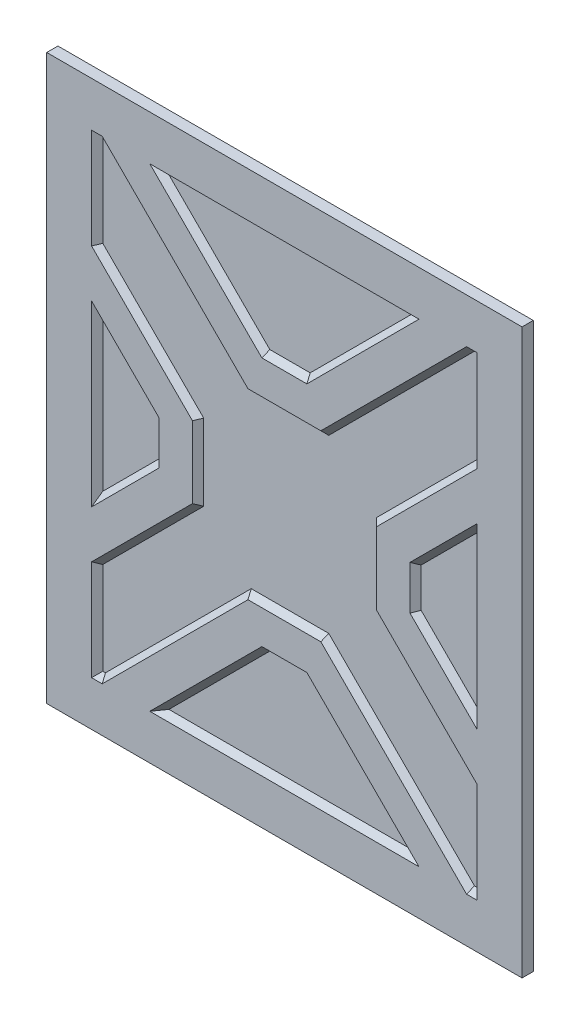
SolidWorks part; units mm, degrees
ref_plane "Plan de face" through (0, 0, 0) normal (0, 0, 1) x (1, 0, 0)
ref_plane "Plan de dessus" through (0, 0, 0) normal (0, 1, 0) x (1, 0, 0)
ref_plane "Plan de droite" through (0, 0, 0) normal (1, 0, 0) x (0, 0, -1)
sketch "Esquisse1" plane through (0, 0, 0) normal (0, 0, 1) x (1, 0, 0)
  line L1 (0, 0) -> (424, 0)
  line L2 (0, 0) -> (0, 503)
  line L3 (0, 503) -> (424, 503)
  line L4 (424, 0) -> (424, 503)
  dimension "D1" = 503
  dimension "D2" = 424
extrude "Boss.-Extru.1" add sketch "Esquisse1" along normal blind 10
sketch "Esquisse2" plane through (0, 0, 10) normal (0, 0, 1) x (1, 0, 0)
  line L0 (179.4975, 333) -> (130, 283.5025) construction
  line L1 (100, 231.9239) -> (100, 271.0761)
  line L2 (100, 271.0761) -> (40, 331.0761)
  line L3 (191.9239, 363) -> (232.0761, 363)
  line L4 (212, 463) -> (212, 40) construction
  line L5 (384, 251.5) -> (40, 251.5) construction
  line L6 (40, 463) -> (40, 373.5025)
  line L7 (40, 373.5025) -> (130, 283.5025)
  line L8 (40, 463) -> (40, 40)
  line L9 (40, 40) -> (384, 40)
  line L10 (384, 40) -> (384, 463)
  line L11 (384, 463) -> (40, 463)
  line L12 (40, 463) -> (40, 40) construction
  line L13 (40, 40) -> (384, 40) construction
  line L14 (384, 40) -> (384, 463) construction
  line L15 (384, 463) -> (40, 463) construction
  line L16 (130, 283.5025) -> (130, 219.4975)
  line L17 (40, 463) -> (49.4975, 463)
  line L18 (49.4975, 463) -> (179.4975, 333)
  line L19 (244.5025, 333) -> (179.4975, 333)
  line L20 (332.0761, 463) -> (91.9239, 463)
  line L21 (91.9239, 463) -> (191.9239, 363)
  line L22 (294, 283.5025) -> (294, 219.4975)
  line L23 (40, 331.0761) -> (40, 171.9239)
  line L24 (324, 231.9239) -> (324, 271.0761)
  line L25 (130, 283.5025) -> (130, 333) construction
  line L26 (130, 333) -> (179.4975, 333) construction
  line L27 (324, 271.0761) -> (384, 331.0761)
  line L28 (384, 331.0761) -> (384, 171.9239)
  line L29 (384, 373.5025) -> (294, 283.5025)
  line L30 (384, 463) -> (384, 373.5025)
  line L31 (384, 463) -> (374.5025, 463)
  line L32 (374.5025, 463) -> (244.5025, 333)
  line L33 (332.0761, 463) -> (232.0761, 363)
  line L34 (100, 231.9239) -> (40, 171.9239)
  line L35 (40, 129.4975) -> (130, 219.4975)
  line L36 (384, 40) -> (374.5025, 40)
  line L37 (384, 40) -> (384, 129.4975)
  line L38 (40, 40) -> (40, 129.4975)
  line L39 (40, 40) -> (49.4975, 40)
  line L40 (332.0761, 40) -> (91.9239, 40)
  line L41 (191.9239, 140) -> (232.0761, 140)
  line L42 (244.5025, 170) -> (179.4975, 170)
  line L43 (91.9239, 40) -> (191.9239, 140)
  line L44 (49.4975, 40) -> (179.4975, 170)
  line L45 (332.0761, 40) -> (232.0761, 140)
  line L46 (374.5025, 40) -> (244.5025, 170)
  line L47 (384, 129.4975) -> (294, 219.4975)
  line L48 (324, 231.9239) -> (384, 171.9239)
  point P20 (212, 333)
  point P23 (294, 251.5)
  point P31 (212, 363)
  point P33 (100, 251.5)
  point P34 (130, 251.5)
  point P47 (324, 251.5)
  dimension "D2" = 90
  dimension "D3" = 130
  dimension "D4" = 70
  dimension "D5" = 45
  dimension "D6" = 30
  dimension "D7" = 30
  dimension "D8" = 30
  dimension "D9" = 30
  dimension "D1" = 40
extrude "Enlèv. mat.-Extru.1" cut sketch "Esquisse2" against normal blind 5
chamfer "Chanfrein1" distance 5 angle 45 36 edges at (212, 40, 5) (141.9239, 90, 5) (212, 140, 5) (282.0761, 90, 5) (40, 251.5, 5) (70, 301.0761, 5) (100, 251.5, 5) (70, 201.9239, 5) (384, 251.5, 5) (354, 201.9239, 5) (324, 251.5, 5) (354, 301.0761, 5) (114.4975, 398, 5) (212, 333, 5) (309.5025, 398, 5) (379.2513, 463, 5) (384, 418.2513, 5) (339, 328.5025, 5) (294, 251.5, 5) (339, 174.4975, 5) (384, 84.7487, 5) (379.2513, 40, 5) (309.5025, 105, 5) (212, 170, 5) (114.4975, 105, 5) (44.7487, 40, 5) (40, 84.7487, 5) (85, 174.4975, 5) (130, 251.5, 5) (85, 328.5025, 5) (40, 418.2513, 5) (44.7487, 463, 5) (212, 463, 5) (282.0761, 413, 5) (212, 363, 5) (141.9239, 413, 5)
